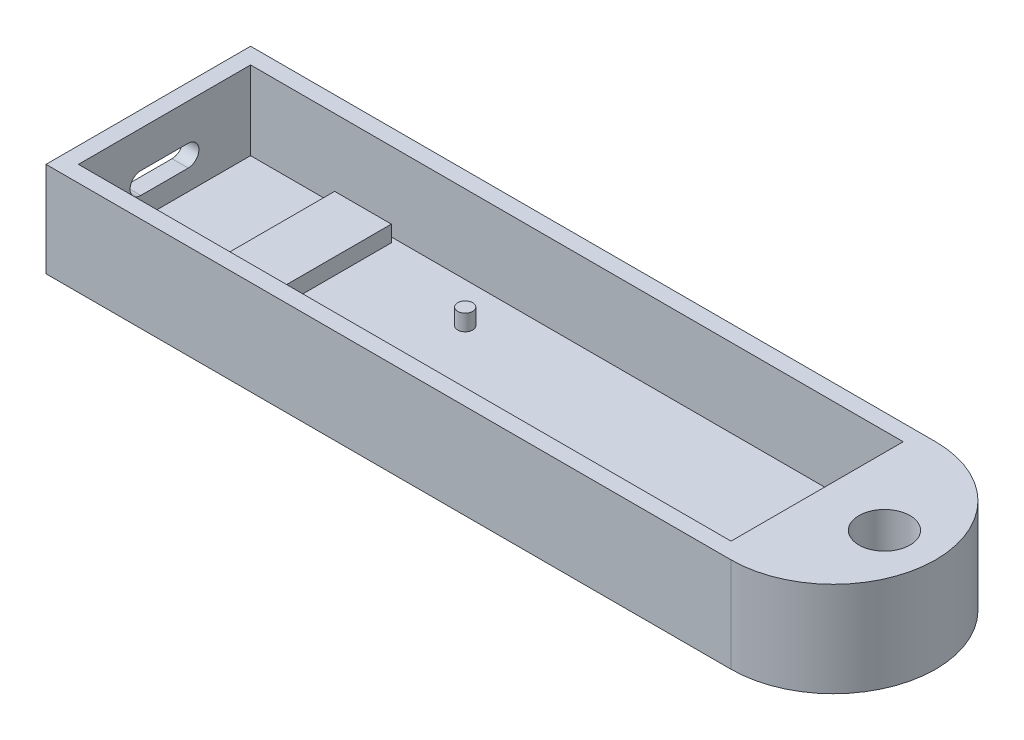
SolidWorks part; units mm, degrees
ref_plane "Front Plane" through (0, 0, 0) normal (0, 0, 1) x (1, 0, 0)
ref_plane "Top Plane" through (0, 0, 0) normal (0, 1, 0) x (1, 0, 0)
ref_plane "Right Plane" through (0, 0, 0) normal (1, 0, 0) x (0, 0, -1)
sketch "Sketch1" plane through (0, 0, 0) normal (0, 1, 0) x (1, 0, 0)
  line L1 (-50.2599, 12.5002) -> (34.2901, 12.5002)
  line L2 (-50.2599, 12.5002) -> (-50.2599, -12.7498)
  line L3 (-50.2599, -12.7498) -> (34.2901, -12.7498)
  line L4 (34.2901, 12.5002) -> (34.2901, -12.7498)
  line L5 (-50.2599, 12.5002) -> (34.2901, -12.7498) construction
  line L6 (-50.2599, -12.7498) -> (34.2901, 12.5002) construction
  line L7 (-48.2599, 10.5002) -> (32.2901, 10.5002)
  line L8 (-48.2599, 10.5002) -> (-48.2599, -10.7498)
  line L9 (-48.2599, -10.7498) -> (32.2901, -10.7498)
  line L10 (32.2901, 10.5002) -> (32.2901, -10.7498)
  line L11 (-48.2599, 10.5002) -> (32.2901, -10.7498) construction
  line L12 (-48.2599, -10.7498) -> (32.2901, 10.5002) construction
  line L13 (-37.2599, -10.1248) -> (-30.2599, -10.1248)
  line L14 (-37.2599, -10.1248) -> (-37.2599, 9.8752)
  line L15 (-37.2599, 9.8752) -> (-30.2599, 9.8752)
  line L16 (-30.2599, -10.1248) -> (-30.2599, 9.8752)
  line L17 (-37.2599, -10.1248) -> (-30.2599, 9.8752) construction
  line L18 (-37.2599, 9.8752) -> (-30.2599, -10.1248) construction
  circle A1 centre (34.2901, -0.1248) radius 12.625
  circle A2 centre (40.6001, -0.1248) radius 3.155
  circle A3 centre (-16.8399, 5.5702) radius 0.925
  circle A4 centre (-16.8399, -7.3814) radius 0.925
  circle A5 centre (30.1601, -7.3814) radius 0.925
  circle A6 centre (30.1601, 5.5702) radius 0.925
  point P0 (-7.9849, -0.1248)
  point P5 (-7.9849, -0.1248)
  point P14 (-33.7599, -0.1248)
  point P19 (-48.2599, -0.1248)
  point P30 (31.6288, 9.3017)
  dimension "D5" = 6.31
  dimension "D10" = 1.85
  dimension "D11" = 1.85
  dimension "D12" = 1.85
  dimension "D13" = 1.85
  dimension "D1" = 25.25
  dimension "D2" = 84.55
  dimension "D3" = 80.55
  dimension "D4" = 21.25
  dimension "D6" = 6.31
  dimension "D7" = 7
  dimension "D8" = 20
  dimension "D9" = 11
  dimension "D14" = 49.13
  dimension "D15" = 4.93
  dimension "D16" = 2.13
extrude "Boss-Extrude2" add sketch "Sketch1" along normal blind 4 contours L13 L16 L15 L14 region at (-33.7599, 0, 0.1248)
extrude "Boss-Extrude3" add sketch "Sketch1<4>" along normal blind 2 contours A1 L7 L8 L9 A4 A3 L16 L13 L14 L15 | L7 A1 L9 L10 A6 A5 region at (-10.2353, 0, 0.1218) region at (27.6108, 0, 0.102)
sketch "Sketch1<4>" plane through (0, 0, 0) normal (0, 1, 0) x (1, 0, 0) same geometry as "Sketch1"
extrude "Boss-Extrude4" add sketch "Sketch1<5>" along normal blind 4 contours A3 | A4 | A5 | A6
sketch "Sketch1<5>" plane through (0, 0, 0) normal (0, 1, 0) x (1, 0, 0) same geometry as "Sketch1"
extrude "Boss-Extrude5" add sketch "Sketch1<6>" along normal blind 11.7 contours A1 L1 L2 L3 L9 L8 L7 | L4 A1 L7 L10 L9 | L4 A1 A2 region at (-7.9849, 0, -11.6178) region at (43.0177, 0, -8.6028) region at (32.809, 0, 0.1248)
sketch "Sketch1<6>" plane through (0, 0, 0) normal (0, 1, 0) x (1, 0, 0) same geometry as "Sketch1"
sketch "Sketch3" plane through (-50.2599, 0, 0) normal (-1, 0, 0) x (0, 0, 1)
  line L0 (-2.8002, 5.85) -> (3.0498, 5.85) construction
  line L1 (-2.8002, 7.175) -> (3.0498, 7.175)
  line L2 (-2.8002, 4.525) -> (3.0498, 4.525)
  line L3 (-12.5002, 0) -> (12.7498, 0) construction
  line L4 (-12.5002, 0) -> (12.7498, 0)
  arc A0 (-2.8002, 7.175) -> (-2.8002, 4.525) centre (-2.8002, 5.85) ccw
  arc A1 (3.0498, 4.525) -> (3.0498, 7.175) centre (3.0498, 5.85) ccw
  point P2 (0.1248, 5.85)
  point P7 (-4.1252, 5.85)
  point P8 (4.3748, 5.85)
  point P10 (0, 0)
  point P13 (0, 0)
  point P14 (0.1248, 0)
  dimension "D3" = 8.5
  dimension "D1" = 5.85
  dimension "D2" = 2.65
extrude "Cut-Extrude1" cut sketch "Sketch3" along normal mid plane 9.7 contours L1 A1 L2 A0
